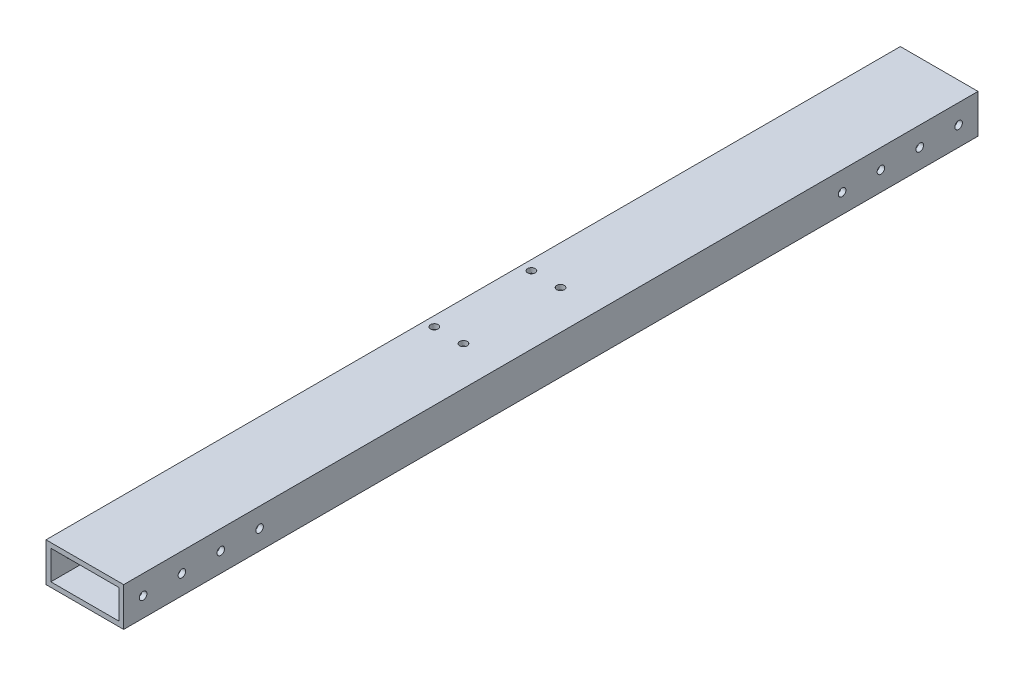
SolidWorks part; units mm, degrees
material "6061-T6 (SS)"
ref_plane "Front Plane" through (0, 0, 0) normal (0, 0, 1) x (1, 0, 0)
ref_plane "Top Plane" through (0, 0, 0) normal (0, 1, 0) x (1, 0, 0)
ref_plane "Right Plane" through (0, 0, 0) normal (1, 0, 0) x (0, 0, -1)
sketch "Sketch1" plane through (0, 0, 0) normal (0, 0, 1) x (1, 0, 0)
  line L1 (-25.4, -12.7) -> (25.4, -12.7)
  line L2 (-25.4, -12.7) -> (-25.4, 12.7)
  line L3 (-25.4, 12.7) -> (25.4, 12.7)
  line L4 (25.4, -12.7) -> (25.4, 12.7)
  line L5 (-25.4, -12.7) -> (25.4, 12.7) construction
  line L6 (-25.4, 12.7) -> (25.4, -12.7) construction
  point P0 (0, 0)
  dimension "D1" = 50.8
  dimension "D2" = 25.4
extrude "Boss-Extrude1" add sketch "Sketch1" along normal mid plane 558.8
shell "Shell1" thickness 3.175 removed face at (0, 0, -279.4) removed face at (0, 0, 279.4)
sketch "Sketch3" plane through (0, 0, 0) normal (1, 0, 0) x (0, 0, -1)
  line L0 (-279.4, -12.7) -> (-279.4, 12.7) construction
  line L1 (0, 12.7) -> (0, -12.7) construction
  line L2 (-279.4, 12.7) -> (279.4, 12.7) construction
  line L3 (-279.4, -12.7) -> (279.4, -12.7) construction
  circle A0 centre (-266.7, 0) radius 2.4892
  circle A1 centre (-241.3, 0) radius 2.4892
  circle A2 centre (-215.9, 0) radius 2.4892
  circle A3 centre (215.9, 0) radius 2.4892
  circle A4 centre (241.3, 0) radius 2.4892
  circle A5 centre (266.7, 0) radius 2.4892
  circle A6 centre (-190.5, 0) radius 2.4892
  circle A7 centre (190.5, 0) radius 2.4892
  dimension "D2" = 4.9784
  dimension "D1" = 12.7
  dimension "D3" = 25.4
  dimension "D4" = 25.4
  dimension "D5" = 12.7
  dimension "D6" = 25.4
extrude "Cut-Extrude1" cut sketch "Sketch3" against normal through all both and the other way through all
sketch "Sketch4" plane through (0, 0, 0) normal (0, 1, 0) x (1, 0, 0)
  line L1 (-25.4, -279.4) -> (-25.4, 279.4) construction
  circle A0 centre (0, -31.75) radius 2.4892
  circle A1 centre (-19.05, -31.75) radius 2.4892
  circle A2 centre (0, 31.75) radius 2.4892
  circle A3 centre (-19.05, 31.75) radius 2.4892
  dimension "D1" = 4.9784
  dimension "D3" = 19.05
  dimension "D4" = 31.75
  dimension "D2" = 6.35
  dimension "D5" = 63.5
extrude "Cut-Extrude2" cut sketch "Sketch4" against normal through all both and the other way through all
equation "\"D4@Sketch3\"=\"D3@Sketch3\""
equation "\"D4@Sketch4\"=1.5-.25"
equation "\"D6@Sketch3\"=\"D3@Sketch3\""
